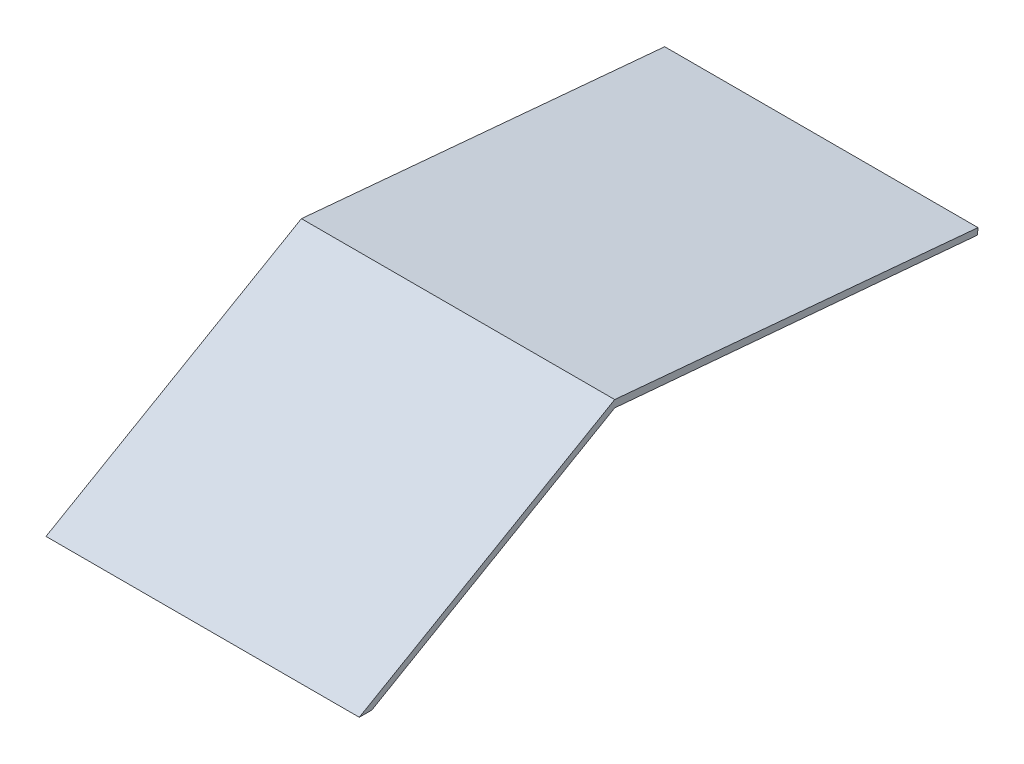
SolidWorks part; units mm, degrees
ref_plane "Front Plane" through (0, 0, 0) normal (0, 0, 1) x (1, 0, 0)
ref_plane "Top Plane" through (0, 0, 0) normal (0, 1, 0) x (1, 0, 0)
ref_plane "Right Plane" through (0, 0, 0) normal (1, 0, 0) x (0, 0, -1)
sketch "Sketch1" plane through (0, 0, 0) normal (1, 0, 0) x (0, 0, -1)
  line L0 (0, 0) -> (80186.3007, 0) construction
  line L1 (0, 0) -> (116.2899, 67.14)
  line L2 (116.2899, 67.14) -> (289.9665, 51.9453)
  line L3 (-6, 0) -> (0, 0)
  line L4 (116.2899, 67.14) -> (116.2899, 70.6041) construction
  line L5 (-6, 0) -> (116.2899, 70.6041)
  line L6 (289.9665, 51.9453) -> (290.2279, 54.9339)
  line L7 (290.2279, 54.9339) -> (116.2899, 70.6041)
  dimension "D1" = 134.28
  dimension "D2" = 30
  dimension "D3" = 145
  dimension "D4" = 174.34
  dimension "D5" = 3
  dimension "D6" = 3
extrude "Boss-Extrude1" add sketch "Sketch1" along normal blind 150
